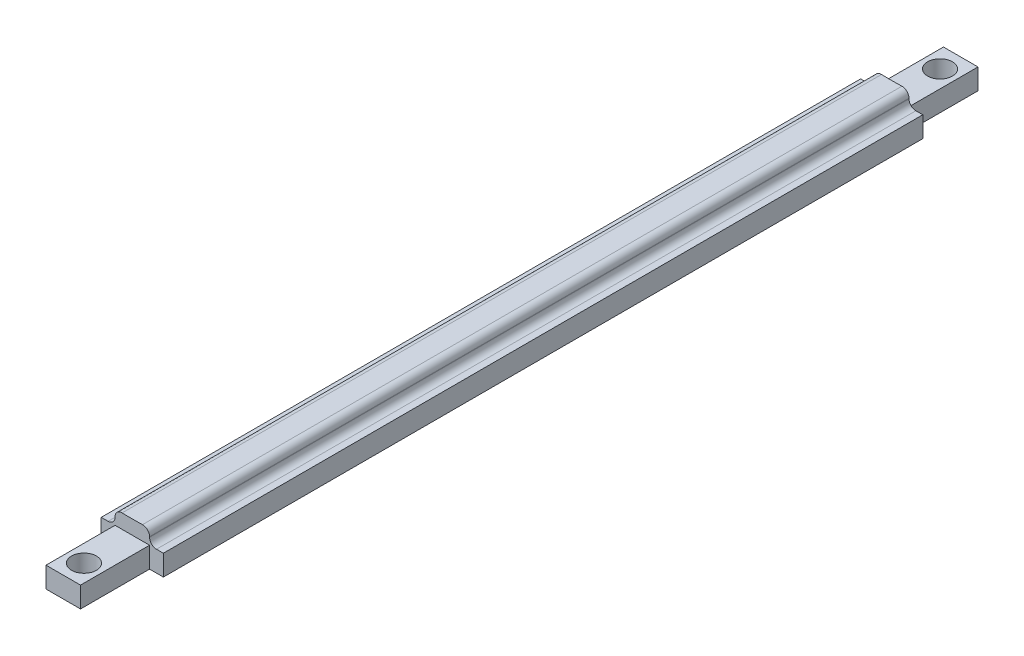
SolidWorks part; units mm, degrees
ref_plane "Front Plane" through (0, 0, 0) normal (0, 0, 1) x (1, 0, 0)
ref_plane "Top Plane" through (0, 0, 0) normal (0, 1, 0) x (1, 0, 0)
ref_plane "Right Plane" through (0, 0, 0) normal (1, 0, 0) x (0, 0, -1)
sketch "Sketch1" plane through (0, 0, 0) normal (0, 1, 0) x (1, 0, 0)
  line L1 (-2.5, -55) -> (2.5, -55)
  line L2 (-2.5, -55) -> (-2.5, 55)
  line L3 (-2.5, 55) -> (2.5, 55)
  line L4 (2.5, -55) -> (2.5, 55)
  line L5 (-2.5, -55) -> (2.5, 55) construction
  line L6 (-2.5, 55) -> (2.5, -55) construction
  point P0 (0, 0)
  dimension "D1" = 5
  dimension "D2" = 110
extrude "Boss-Extrude1" add sketch "Sketch1" along normal blind 3
ref_plane "Plane3" through (0, 0, 0) normal (0, 0, 1) x (1, 0, 0)
sketch "Sketch3" plane through (0, 0, 0) normal (0, 0, 1) x (1, 0, 0)
  line L0 (-2.5, 3) -> (-2.5, 5.103)
  line L1 (-2.5, 5.103) -> (2.5, 5.103) construction
  line L2 (2.5, 5.103) -> (2.5, 3)
  line L3 (0, 5.103) -> (0, 64.05) construction
  line L4 (-2.5, 0) -> (2.5, 0)
  line L5 (2.5, 0) -> (2.5, 3)
  line L6 (2.5, 3) -> (-2.5, 3)
  line L7 (-2.5, 3) -> (-2.5, 0)
  line L8 (-2.5, 0) -> (2.5, 0)
  line L9 (2.5, 0) -> (2.5, 3)
  line L11 (-2.5, 3) -> (-2.5, 0)
  arc A0 (-2.5, 5.103) -> (2.5, 5.103) centre (0, 64.05) ccw
  dimension "D1" = 0
extrude "Boss-Extrude2" add sketch "Sketch3" along normal up to surface (55 mm away) up to face at (0, 1.5, 55)
sketch "Sketch7" plane through (0, 0, 0) normal (0, 0, -1) x (-1, 0, 0)
  line L3 (-2.5, 5.103) -> (-2.5, 3)
  line L4 (-2.5, 3) -> (2.5, 3)
  line L5 (2.5, 3) -> (2.5, 5.103)
  line L6 (-2.5, 5.103) -> (-2.5, 3)
  line L7 (-2.5, 3) -> (2.5, 3)
  line L8 (2.5, 3) -> (2.5, 5.103)
  arc A1 (-2.5, 5.103) -> (2.5, 5.103) centre (0, 64.05) ccw
  arc A2 (-2.5, 5.103) -> (2.5, 5.103) centre (0, 64.05) ccw
  dimension "D1" = 0
extrude "Boss-Extrude3" add sketch "Sketch7" along normal up to surface (55 mm away) up to face at (0, 1.5, -55)
sketch "Sketch8" plane through (0, 0, 0) normal (0, -1, 0) x (1, 0, 0)
  line L0 (2.5, 55) -> (2.5, -55) construction
  line L1 (-2.5, 55) -> (2.5, 55)
  line L2 (-2.5, 55) -> (-2.5, 65)
  line L3 (-2.5, 65) -> (2.5, 65)
  line L4 (2.5, 55) -> (2.5, 65)
  line L5 (0, 0) -> (17.0745, 0) construction
  line L6 (-2.5, -65) -> (2.5, -65)
  line L7 (2.5, -55) -> (2.5, -65)
  line L8 (-2.5, -55) -> (2.5, -55)
  line L9 (-2.5, -55) -> (-2.5, -65)
  dimension "D1" = 10
extrude "Boss-Extrude4" add sketch "Sketch8" against normal blind 3
sketch "Sketch6" plane through (0, 3, 0) normal (0, 1, 0) x (1, 0, 0)
  line L0 (0, -65) -> (0, -62) construction
  line L2 (0, 0) -> (12.4428, 0) construction
  line L3 (-5.6053, 0) -> (5.6053, 0) construction
  line L4 (2.5, -65) -> (-2.5, -65) construction
  circle A0 centre (0, -62) radius 1.8
  circle A1 centre (0, 62) radius 1.8
  dimension "D1" = 3.6
  dimension "D2" = 3
extrude "Cut-Extrude1" cut sketch "Sketch6" against normal through all
sketch "Sketch9" plane through (0, 0, 0) normal (0, -1, 0) x (1, 0, 0)
  line L0 (2.5, -55) -> (-2.5, -55) construction
  line L1 (-2.5, 55) -> (2.5, 55) construction
  line L2 (2.5, -55) -> (-2.5, -55) construction
  line L3 (-2.5, 55) -> (2.5, 55) construction
  line L4 (-2.5, -65) -> (-2.5, 65) construction
  line L5 (-4.5, -55) -> (4.5, -55)
  line L6 (-4.5, -55) -> (-4.5, 55)
  line L7 (-4.5, 55) -> (4.5, 55)
  line L8 (4.5, -55) -> (4.5, 55)
  line L9 (-2.5, -65) -> (-2.5, 65) construction
  point P8 (0, -55)
  point P9 (0, -55)
  point P10 (0, 55)
  point P11 (0, 55)
  dimension "D1" = 2
extrude "Boss-Extrude5" add sketch "Sketch9" against normal up to surface (3 mm away) up to face at (0, 3, 63.8)
fillet "Fillet1" radius 1 4 edges at (-2.5, 5.103, 0) (2.5, 5.103, 0) (2.5, 3, 0) (-2.5, 3, 0)
